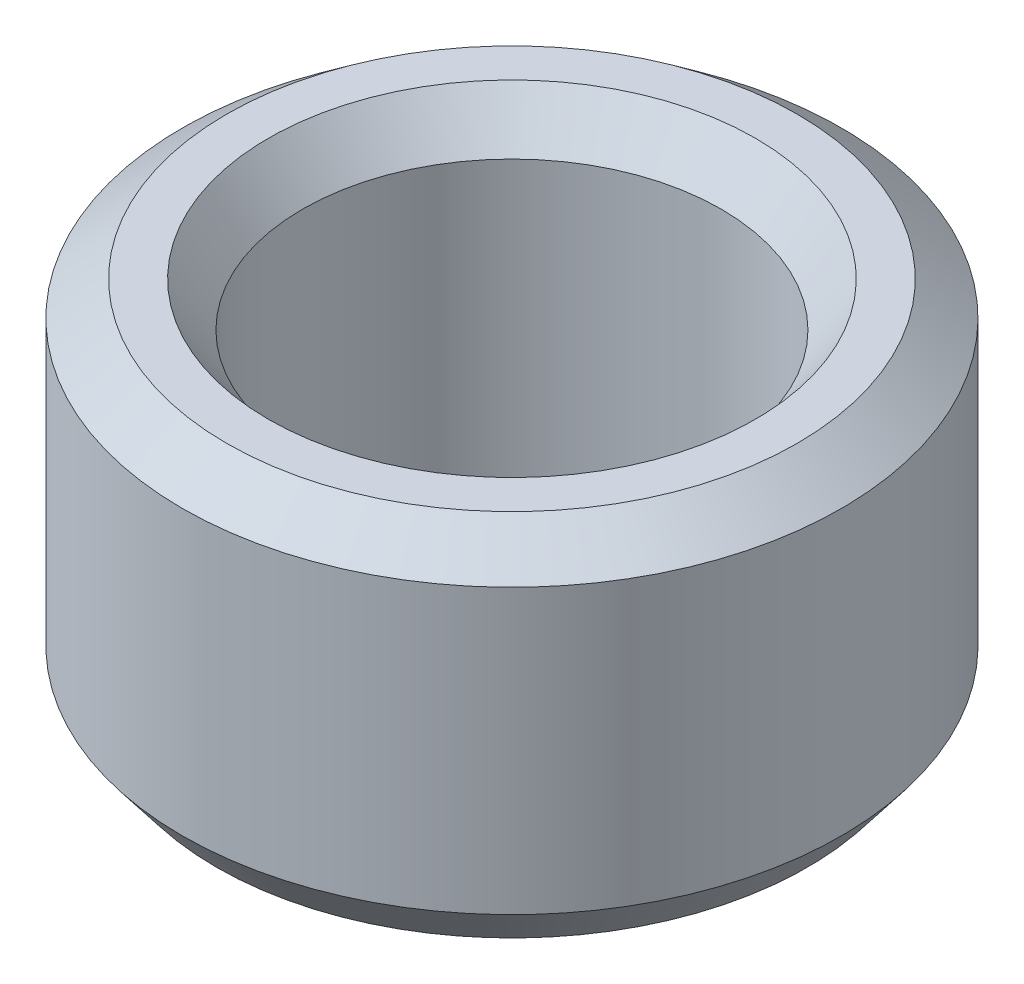
SolidWorks part; units mm, degrees
ref_plane "Front Plane" through (0, 0, 0) normal (0, 0, 1) x (1, 0, 0)
ref_plane "Top Plane" through (0, 0, 0) normal (0, 1, 0) x (1, 0, 0)
ref_plane "Right Plane" through (0, 0, 0) normal (1, 0, 0) x (0, 0, -1)
sketch "Sketch1" plane through (0, 0, 0) normal (0, 1, 0) x (1, 0, 0)
  circle A0 centre (0, 0) radius 37.5
  dimension "SLEEVE_OD" = 75
extrude "Boss-Extrude1" add sketch "Sketch1" along normal blind 41.1938
sketch "Sketch2" plane through (0, 0, 0) normal (0, 1, 0) x (1, 0, 0)
  circle A0 centre (0, 0) radius 23.819
  dimension "BORE_D" = 47.6379
extrude "Cut-Extrude1" cut sketch "Sketch2" along normal through all
chamfer "Chamfer1" distance 3.8862 angle 52.398 4 edges at (0, 41.1938, 23.819) (0, 0, 23.819) (0, 0, 37.5) (0, 41.1938, 37.5) first distance on face at (0, 41.1938, 23.819) first distance on face at (0, 0, 23.819) first distance on face at (0, 41.1938, 37.5)
